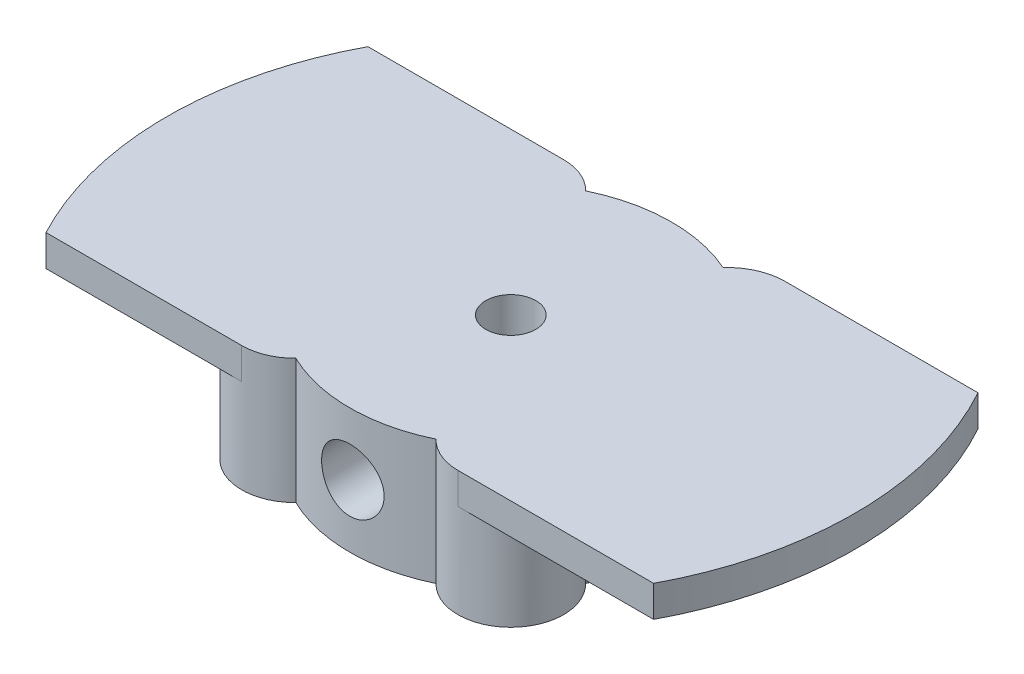
SolidWorks part; units mm, degrees
ref_plane "Front Plane" through (0, 0, 0) normal (0, 0, 1) x (1, 0, 0)
ref_plane "Top Plane" through (0, 0, 0) normal (0, 1, 0) x (1, 0, 0)
ref_plane "Right Plane" through (0, 0, 0) normal (1, 0, 0) x (0, 0, -1)
sketch "Sketch1" plane through (0, 0, 0) normal (0, 1, 0) x (1, 0, 0)
  line L0 (-10.3, 0) -> (-10.3, -6.915) construction
  line L1 (-6.915, -6.915) -> (6.915, -6.915) construction
  line L2 (-6.915, -6.915) -> (-6.915, 6.915) construction
  line L3 (-6.915, 6.915) -> (6.915, 6.915) construction
  line L4 (6.915, -6.915) -> (6.915, 6.915) construction
  line L5 (-6.915, -6.915) -> (6.915, 6.915) construction
  line L6 (-6.915, 6.915) -> (6.915, -6.915) construction
  arc A5 (-9.272, -4.4855) -> (-4.4855, -9.272) centre (-6.915, -6.915) ccw
  arc A6 (4.4855, -9.272) -> (9.272, -4.4855) centre (6.915, -6.915) ccw
  arc A7 (9.4218, 4.1617) -> (4.1617, 9.4218) centre (6.915, 6.915) ccw
  arc A8 (-4.4855, 9.272) -> (-9.272, 4.4855) centre (-6.915, 6.915) ccw
  arc A9 (-4.4855, -9.272) -> (4.4855, -9.272) centre (0, 0) ccw
  arc A10 (9.272, -4.4855) -> (9.4218, 4.1617) centre (0, 0) ccw
  arc A11 (4.1617, 9.4218) -> (-4.4855, 9.272) centre (0, 0) ccw
  arc A12 (-9.272, 4.4855) -> (-9.272, -4.4855) centre (0, 0) ccw
  circle A13 centre (0, 0) radius 1.6
  dimension "D1" = 10.3
  dimension "D3" = 3.2
  dimension "D2" = 13.83
extrude "Boss-Extrude1" add sketch "Sketch1" along normal blind 8
sketch "Sketch3" plane through (0, 0, 0) normal (0, 0, 1) x (1, 0, 0)
  line L0 (0, 0) -> (0, 4) construction
  line L1 (-4.4855, 0) -> (4.4855, 0) construction
  circle A0 centre (0, 4) radius 2
  dimension "D1" = 4
  dimension "D2" = 4
extrude "Cut-Extrude1" cut sketch "Sketch3" along normal blind 14.5
sketch "Sketch4" plane through (0, 8, 0) normal (0, 1, 0) x (1, 0, 0)
  line L0 (-19.4399, 10.3) -> (-6.915, 10.3)
  line L1 (19.2567, 10.6385) -> (6.915, 10.6385)
  line L2 (-19.4399, -10.3) -> (-6.915, -10.3)
  line L3 (19.4399, -10.3) -> (6.915, -10.3)
  arc A0 (-19.4399, 10.3) -> (-19.4399, -10.3) centre (0, 0) ccw
  arc A1 (-4.4855, 9.272) -> (-9.272, 4.4855) centre (-6.915, 6.915) ccw construction
  arc A2 (9.4218, 4.1617) -> (4.1617, 9.4218) centre (6.915, 6.915) ccw construction
  arc A3 (-9.272, -4.4855) -> (-4.4855, -9.272) centre (-6.915, -6.915) ccw construction
  arc A4 (4.4855, -9.272) -> (9.272, -4.4855) centre (6.915, -6.915) ccw construction
  arc A5 (19.4399, -10.3) -> (19.2567, 10.6385) centre (0, 0) ccw
  arc A6 (-6.915, 10.3) -> (-9.272, 4.4855) centre (-6.915, 6.915) ccw
  arc A7 (-9.272, 4.4855) -> (-9.272, -4.4855) centre (0, 0) ccw
  arc A8 (-6.915, -10.3) -> (-9.272, -4.4855) centre (-6.915, -6.915) cw
  arc A9 (6.915, -10.3) -> (9.272, -4.4855) centre (6.915, -6.915) ccw
  arc A10 (9.4218, 4.1617) -> (9.272, -4.4855) centre (0, 0) cw
  arc A11 (6.915, 10.6385) -> (9.4218, 4.1617) centre (6.915, 6.915) cw
  dimension "D1" = 44
extrude "Boss-Extrude3" add sketch "Sketch4" against normal blind 2
sketch "Sketch5" plane through (0, 0, 0) normal (0, -1, 0) x (1, 0, 0)
  circle A0 centre (-6.915, 6.915) radius 2.25
  circle A1 centre (6.915, 6.915) radius 2.25
  circle A2 centre (6.915, -6.915) radius 2.25
  circle A3 centre (-6.915, -6.915) radius 2.25
  point P12 (-6.915, 6.915)
  point P14 (6.915, 6.915)
  point P16 (6.915, -6.915)
  point P18 (-6.915, -6.915)
  dimension "D1" = 4.5
extrude "Cut-Extrude2" cut sketch "Sketch5" against normal blind 6.3
